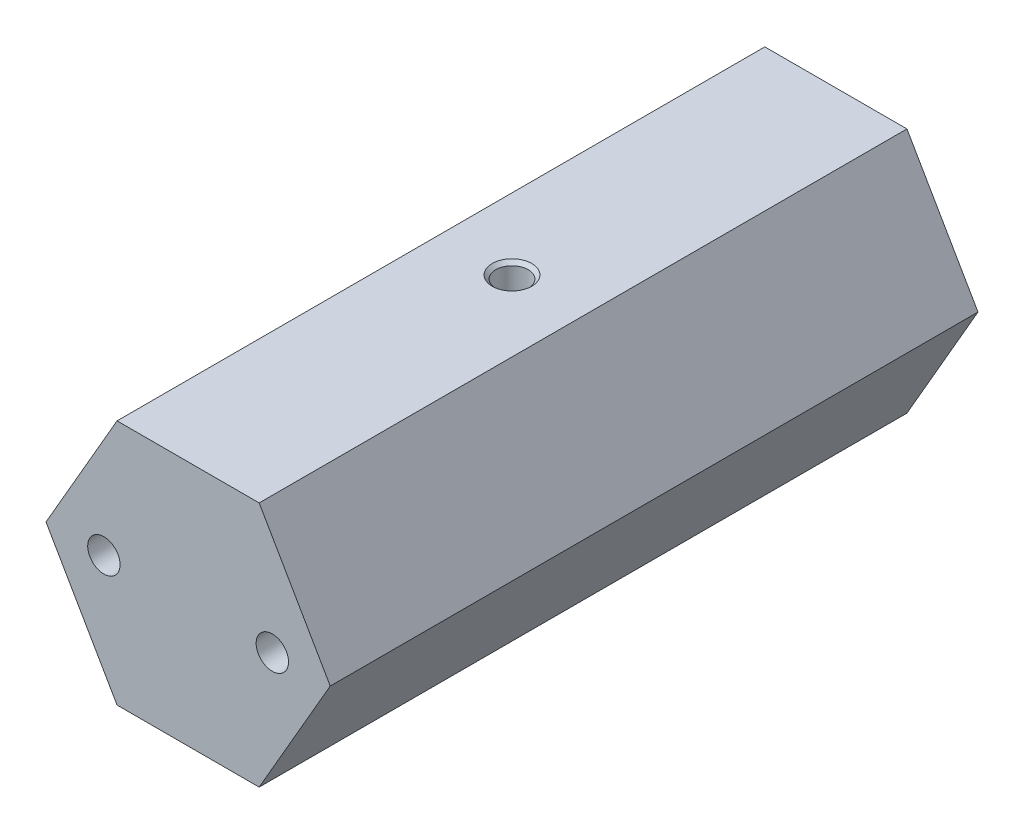
SolidWorks part; units mm, degrees
material "6061-T6 (SS)"
ref_plane "Front Plane" through (0, 0, 0) normal (0, 0, 1) x (1, 0, 0)
ref_plane "Top Plane" through (0, 0, 0) normal (0, 1, 0) x (1, 0, 0)
ref_plane "Right Plane" through (0, 0, 0) normal (1, 0, 0) x (0, 0, -1)
sketch "Sketch1" plane through (0, 0, 0) normal (0, 0, 1) x (1, 0, 0)
  line L1 (-5.4848, -9.5) -> (5.4848, -9.5)
  line L2 (5.4848, -9.5) -> (10.9697, 0)
  line L3 (10.9697, 0) -> (5.4848, 9.5)
  line L4 (5.4848, 9.5) -> (-5.4848, 9.5)
  line L5 (-5.4848, 9.5) -> (-10.9697, 0)
  line L6 (-10.9697, 0) -> (-5.4848, -9.5)
  circle A0 centre (0, 0) radius 9.5 construction
  circle A1 centre (-6.5, 0) radius 1.25
  circle A2 centre (-6.5, 0) radius 1.5 construction
  circle A3 centre (6.5, 0) radius 1.25
  circle A4 centre (6.5, 0) radius 1.5 construction
  point P20 (0, 0)
  dimension "D1" = 2.5
  dimension "D2" = 3
  dimension "D3" = 2
  dimension "D4" = 19
  dimension "D5" = 13
extrude "Boss-Extrude1" add sketch "Sketch1" along normal mid plane 50
sketch "Sketch2" plane through (0, 9.5, 0) normal (0, 1, 0) x (1, 0, 0)
  point P0 (0, 0)
hole_wizard "M3x0.5 Tapped Hole1" positions "Sketch2" profile "Sketch3" tap size "M3x0.5" standard "ANSI Metric" end condition up to next
sketch "Sketch3" plane through (0, 9.5, 0) normal (1, 0, 0) x (0, 0, 1)
  line L0 (0, 0) -> (0, 19)
  line L1 (0, 19) -> (1.25, 19)
  line L2 (1.25, 19) -> (1.25, 0.275)
  line L3 (1.25, 0.275) -> (1.525, 0)
  line L5 (1.525, 0) -> (0, 0)
  line L6 (-1.25, 0.275) -> (-1.525, 0) construction
  line L11 (0, -6.35) -> (0, 107.95) construction
  dimension "Thru Tap Drill Dia." = 2.5
  dimension "Thru Tap Drill Depth" = 19
  dimension "Near C'Sink Dia." = 3.05
  dimension "Near C'Sink Angle" = 90
cosmetic thread "Hole Thread1" parameters "D2"=3
